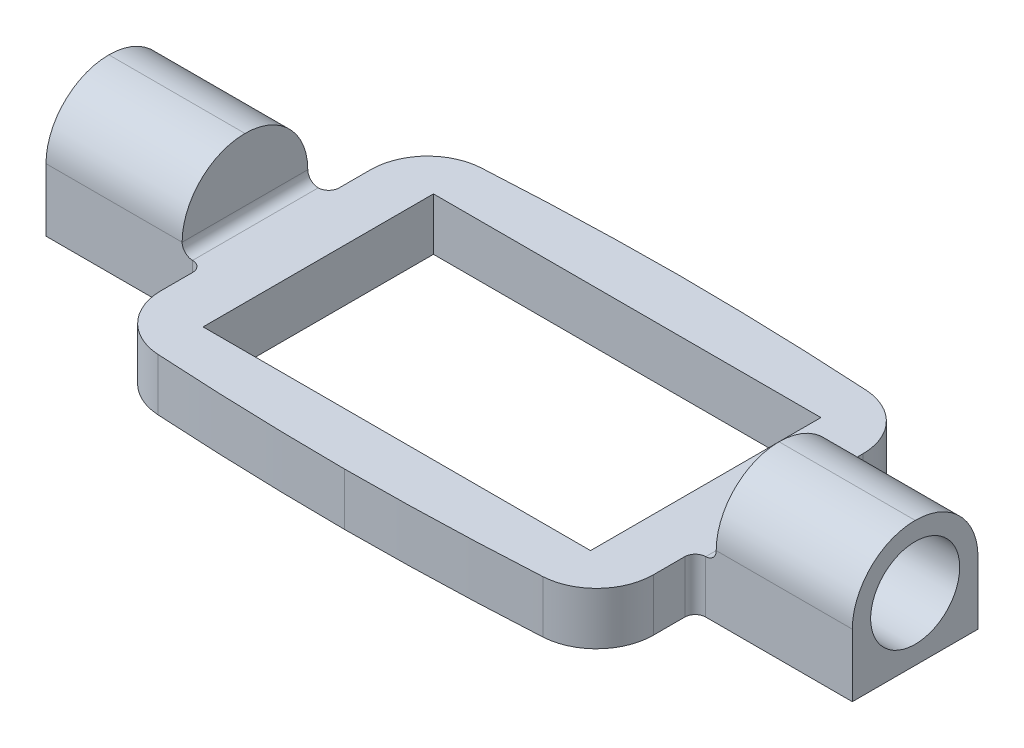
SolidWorks part; units mm, degrees
ref_plane "Front Plane" through (0, 0, 0) normal (0, 0, 1) x (1, 0, 0)
ref_plane "Top Plane" through (0, 0, 0) normal (0, 1, 0) x (1, 0, 0)
ref_plane "Right Plane" through (0, 0, 0) normal (1, 0, 0) x (0, 0, -1)
sketch "Sketch2" plane through (0, 0, 0) normal (0, 1, 0) x (1, 0, 0)
  line L0 (-46.99, 27.94) -> (-93.6881, -11.2443) construction
  line L1 (0, 0) -> (-93.98, 0)
  line L2 (0, 0) -> (0, 55.88)
  line L3 (0, 55.88) -> (-93.98, 55.88)
  line L4 (-93.98, 0) -> (-93.98, 55.88)
  line L5 (-46.99, 55.88) -> (-46.99, 27.94) construction
  line L6 (-46.99, 27.94) -> (-0.2919, -11.2443) construction
  line L7 (-46.99, 27.94) -> (-219.5694, 27.94) construction
  line L8 (-44.4992, -12.7) -> (-49.4808, -12.7)
  line L9 (-144.78, 12.7) -> (-106.68, 12.7)
  line L10 (-46.99, 27.94) -> (69.9568, 27.94) construction
  line L11 (-106.68, 2.54) -> (-106.68, 12.7)
  line L12 (-144.78, 12.7) -> (-144.78, 43.18)
  line L13 (12.7, 2.54) -> (12.7, 12.7)
  line L14 (12.7, 12.7) -> (50.8, 12.7)
  line L15 (50.8, 12.7) -> (50.8, 43.18)
  line L16 (12.7, 43.18) -> (50.8, 43.18)
  line L17 (12.7, 53.34) -> (12.7, 43.18)
  line L18 (-106.68, 53.34) -> (-106.68, 43.18)
  line L19 (-144.78, 43.18) -> (-106.68, 43.18)
  arc A0 (-44.4992, -12.7) -> (-93.6881, -11.2443) centre (-44.4992, 819.1044) cw
  arc A1 (-93.6881, -11.2443) -> (-106.68, 2.54) centre (-92.8715, 2.54) cw
  arc A2 (-49.4808, -12.7) -> (-0.2919, -11.2443) centre (-49.4808, 819.1044) ccw
  arc A3 (-0.2919, -11.2443) -> (12.7, 2.54) centre (-1.1085, 2.54) ccw
  arc A4 (-0.2919, 67.1243) -> (12.7, 53.34) centre (-1.1085, 53.34) cw
  arc A5 (-49.4808, 68.58) -> (-0.2919, 67.1243) centre (-49.4808, -763.2244) cw
  arc A6 (-44.4992, 68.58) -> (-93.6881, 67.1243) centre (-44.4992, -763.2244) ccw
  arc A7 (-93.6881, 67.1243) -> (-106.68, 53.34) centre (-92.8715, 53.34) ccw
  point P7 (0, 27.94)
  point P8 (-46.99, 55.88)
  point P25 (12.7, 27.94)
  point P29 (50.8, 27.94)
  point P34 (-106.68, 27.94)
  point P43 (-144.78, 27.94)
  dimension "D9" = 25.4
  dimension "D1" = 93.98
  dimension "D2" = 55.88
  dimension "D3" = 130
  dimension "D4" = 130
  dimension "D5" = 60.96
  dimension "D6" = 60.96
  dimension "D7" = 15.24
  dimension "D8" = 12.7
  dimension "D10" = 10.16
  dimension "D11" = 25.4
  dimension "D12" = 15.24
  dimension "D13" = 10.16
  dimension "D14" = 38.1
  dimension "D15" = 38.1
  dimension "D16" = 12.7
  dimension "D17" = 12.7
extrude "Boss-Extrude1" add sketch "Sketch2" along normal blind 12.7 contours A1 A0 A2 A3 L1 L4 L3 L2 region at (-70.2834, 0, 10.1813)
sketch "Sketch3" plane through (0, 12.7, 0) normal (0, 1, 0) x (1, 0, 0)
  line L0 (-46.99, 68.5763) -> (-46.99, -12.6963) construction
  line L1 (12.7, 12.7) -> (50.8, 12.7) construction
  line L2 (50.8, 43.18) -> (17.78, 43.18)
  line L3 (50.8, 43.18) -> (50.8, 12.7)
  line L4 (50.8, 12.7) -> (17.78, 12.7)
  line L5 (17.78, 43.18) -> (17.78, 12.7)
  line L6 (-144.78, 12.7) -> (-111.76, 12.7)
  line L7 (-111.76, 43.18) -> (-111.76, 12.7)
  line L8 (-144.78, 43.18) -> (-111.76, 43.18)
  line L9 (-144.78, 43.18) -> (-144.78, 12.7)
  dimension "D1" = 33.02
extrude "Boss-Extrude2" add sketch "Sketch3" along normal blind 17.78
fillet "Fillet1" radius 2.54 2 edges at (17.78, 12.7, -27.94) (-111.76, 12.7, -27.94)
sketch "Sketch4" plane through (50.8, 0, 0) normal (1, 0, 0) x (0, 0, -1)
  line L1 (12.7, 30.48) -> (12.7, 0) construction
  line L2 (12.7, 30.48) -> (43.18, 30.48) construction
  circle A0 centre (27.94, 15.24) radius 10.795
  point P4 (12.7, 15.24)
  point P7 (27.94, 30.48)
  dimension "D1" = 21.59
extrude "Cut-Extrude1" cut sketch "Sketch4" against normal blind 25.4
sketch "Sketch5" plane through (-144.78, 0, 0) normal (-1, 0, 0) x (0, 0, 1)
  line L0 (-43.18, 30.48) -> (-43.18, 0) construction
  line L1 (-43.18, 30.48) -> (-12.7, 30.48) construction
  circle A0 centre (-27.94, 15.24) radius 10.795
  point P2 (0, 0)
  point P5 (-43.18, 15.24)
  point P8 (-27.94, 30.48)
  dimension "D1" = 21.59
extrude "Cut-Extrude2" cut sketch "Sketch5" against normal blind 25.4
fillet "Fillet2" radius 2.54 4 edges at (12.7, 6.35, -43.18) (12.7, 6.35, -12.7) (-106.68, 6.35, -43.18) (-106.68, 6.35, -12.7)
fillet "Fillet3" radius 15.24 4 edges at (34.29, 30.48, -43.18) (34.29, 30.48, -12.7) (-128.27, 30.48, -43.18) (-128.27, 30.48, -12.7)
